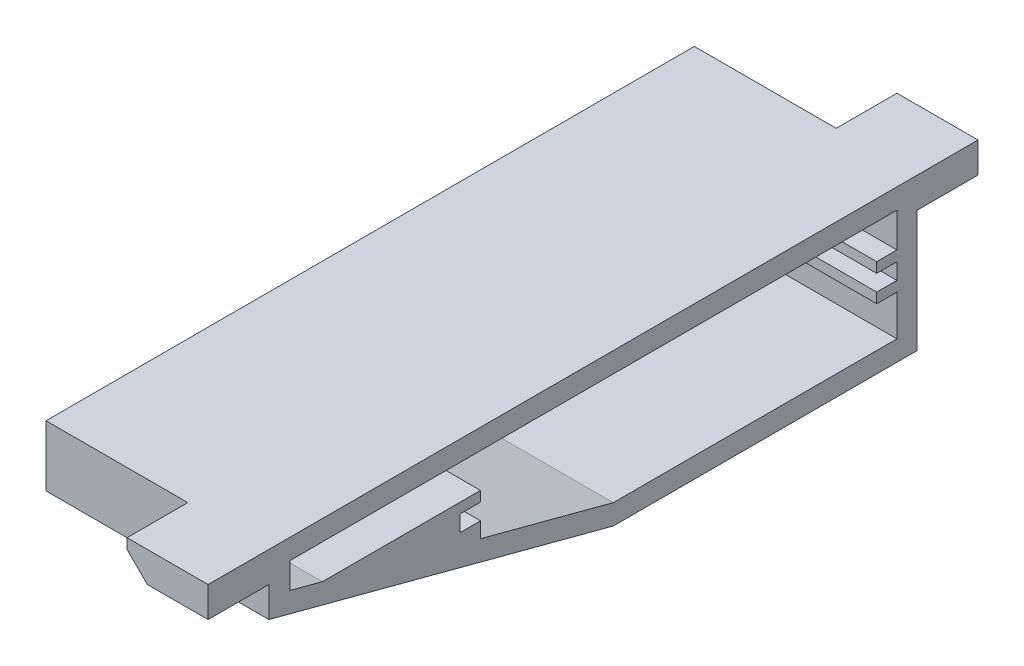
SolidWorks part; units mm, degrees
ref_plane "前视基准面" through (0, 0, 0) normal (0, 0, 1) x (1, 0, 0)
ref_plane "上视基准面" through (0, 0, 0) normal (0, 1, 0) x (1, 0, 0)
ref_plane "右视基准面" through (0, 0, 0) normal (1, 0, 0) x (0, 0, -1)
sketch "草图1" plane through (0, 0, 0) normal (0, 0, 1) x (1, 0, 0)
  line L0 (0, 0) -> (22, 0)
  line L1 (0, 0) -> (0, 15)
  line L2 (0, 15) -> (22, 15)
  line L3 (22, 15) -> (22, 0)
extrude "凸台-拉伸1" add sketch "草图1" along normal blind 2
sketch "草图2" plane through (0, 0, 0) normal (0, -1, 0) x (1, 0, 0)
  line L0 (0, 0) -> (0, 30)
  line L2 (22, 0) -> (22, 30)
  line L3 (22, 30) -> (0, 30)
  line L4 (0, 0) -> (22, 0)
extrude "凸台-拉伸2" add sketch "草图2" against normal blind 2
sketch "草图3" plane through (0, 0, 0) normal (-1, 0, 0) x (0, 0, 1)
  line L0 (0, 15) -> (64, 15)
  line L3 (0, 15) -> (0, 0) construction
  line L4 (0, 13) -> (0, 15)
  line L5 (64, 15) -> (64, 9)
  line L6 (64, 8) -> (64, 15) construction
  line L7 (30, 0) -> (64, 9)
  line L8 (61.932, 10.4526) -> (61.932, 13)
  line L10 (30, 2) -> (61.932, 10.4526)
  line L11 (61.932, 13) -> (0, 13)
  line M4 (30, 0) -> (30, 2)
  line M6 (2, 2) -> (2, 15)
  line M7 (2, 15) -> (0, 15)
  line M8 (0, 15) -> (0, 0)
extrude "凸台-拉伸3" add sketch "草图3" against normal blind 22 contours L11 L8 L10 L7 L5 L0 M4 M6 | L11 M6 M7 M8 region at (0, 14, 1) region at (0, 14.3621, 33)
sketch "草图4" plane through (0, 0, 64) normal (0, 0, 1) x (1, 0, 0)
  line L1 (22, 15) -> (14, 15)
  line L2 (22, 15) -> (22, 12)
  line L3 (22, 12) -> (14, 12)
  line L4 (14, 15) -> (14, 12)
extrude "凸台-拉伸4" add sketch "草图4" along normal blind 6
sketch "草图5" plane through (0, 0, 0) normal (0, 0, -1) x (-1, 0, 0)
  line L1 (-22, 15) -> (-14, 15)
  line L2 (-22, 15) -> (-22, 12)
  line L3 (-22, 12) -> (-14, 12)
  line L4 (-14, 15) -> (-14, 12)
extrude "凸台-拉伸5" add sketch "草图5" along normal blind 6
chamfer "倒角1" distance 2 angle 45 2 edges at (14, 12, 67) (14, 12, -3)
sketch "草图6" plane through (0, 0, 0) normal (-1, 0, 0) x (0, 0, 1)
  line L1 (2, 13) -> (2, 2) construction
  line L2 (2, 6) -> (4, 6)
  line L3 (4, 6) -> (4, 7)
  line L4 (4, 7) -> (2, 7)
  line L5 (2, 9.6) -> (2, 8.6)
  line L6 (2, 8.6) -> (4, 8.6)
  line L7 (4, 8.6) -> (4, 9.6)
  line L8 (4, 9.6) -> (2, 9.6)
  line L9 (2, 7) -> (2, 6)
  line L10 (30, 2) -> (61.932, 10.4526) construction
  line L12 (45.1111, 7) -> (45.1111, 8.6)
  line L13 (45.1111, 8.6) -> (43.1111, 8.6)
  line L14 (43.1111, 8.6) -> (43.1111, 9.6)
  line L15 (43.1111, 9.6) -> (58.7111, 9.6)
  line L16 (45.1111, 7) -> (43.1111, 7)
  line L17 (43.1111, 7) -> (43.1111, 5.4706)
  line L18 (43.1111, 5.4706) -> (58.7111, 9.6)
extrude "凸台-拉伸6" add sketch "草图6" against normal blind 22
